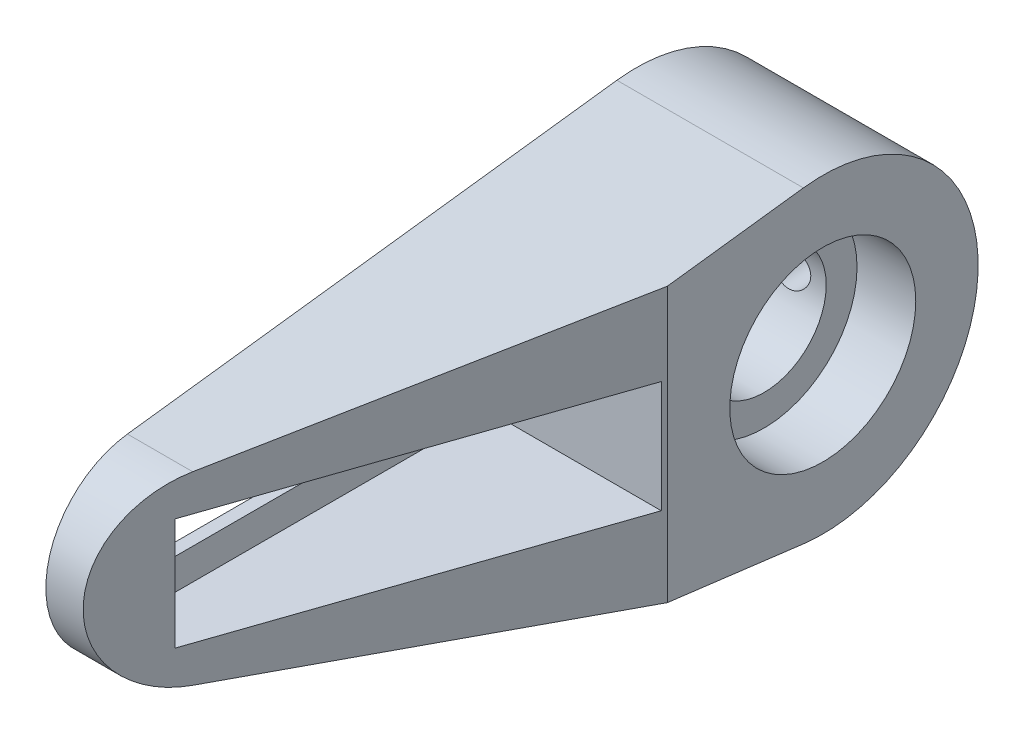
SolidWorks part; units mm, degrees
material "PLA"
ref_plane "Front Plane" through (0, 0, 0) normal (0, 0, 1) x (1, 0, 0)
ref_plane "Top Plane" through (0, 0, 0) normal (0, 1, 0) x (1, 0, 0)
ref_plane "Right Plane" through (0, 0, 0) normal (1, 0, 0) x (0, 0, -1)
sketch "Sketch1" plane through (0, 0, 0) normal (1, 0, 0) x (0, 0, -1)
  circle A0 centre (0, 0) radius 9.5
  circle A1 centre (0, 0) radius 15.875
  circle A2 centre (0, 0) radius 6.35
  dimension "D1" = 19
  dimension "D2" = 31.75
  dimension "D3" = 12.7
extrude "Boss-Extrude1" add sketch "Sketch1" along normal blind 6 contours A1 A0 region at (0, 0, 15.426)
extrude "Boss-Extrude2" add sketch "Sketch1<3>" against normal blind 13.05 contours A0 A2 | A1 A0 region at (0, 0, 9.2313) region at (0, 0, 15.426)
sketch "Sketch1<3>" plane through (0, 0, 0) normal (1, 0, 0) x (0, 0, -1) same geometry as "Sketch1"
sketch "Sketch2" plane through (-13.05, 0, 0) normal (-1, 0, 0) x (0, 0, 1)
  line L0 (0, 0) -> (11.1567, 0) construction
  circle A0 centre (0, 12.7) radius 1.95
  circle A1 centre (0, 0) radius 15.875
  circle A2 centre (0, 0) radius 15.875
  circle A3 centre (0, -12.7) radius 1.95
  dimension "D2" = 3.9
  dimension "D3" = 12.7
  dimension "D1" = 0
extrude "Cut-Extrude1" cut sketch "Sketch2" against normal blind 10.16 contours A0 | A3 region at (-13.05, 12.7, 0) region at (-13.05, -12.7, 0)
ref_plane "Plane1" through (0, 0, -15.875) normal (0, 0, 1) x (1, 0, 0)
sketch "Sketch3" plane through (0, 0, -15.875) normal (0, 0, 1) x (1, 0, 0)
  line L0 (-3.525, 0) -> (5.8573, 0) construction
  line L1 (-3.525, 0) -> (-3.525, 15.875) construction
  line L2 (6, 15.875) -> (-13.05, 15.875) construction
  circle A0 centre (-3.525, 0) radius 1.95
  dimension "D1" = 3.9
extrude "Cut-Extrude2" cut sketch "Sketch3" along normal up to surface (9.525 mm away) up to face at (-13.05, 0, -6.35)
sketch "Sketch4" plane through (6, 0, 0) normal (1, 0, 0) x (0, 0, -1)
  line L0 (-1.9844, 15.7505) -> (-51.9906, 9.4503)
  line L1 (0, 0) -> (-50.8, 0) construction
  line L2 (-1.9844, -15.7505) -> (-51.9906, -9.4503)
  circle A0 centre (0, 0) radius 15.875 construction
  circle A1 centre (-50.8, 0) radius 9.525
  circle M6 centre (0, 0) radius 15.875
  dimension "D1" = 50.8
  dimension "D2" = 19.05
extrude "Boss-Extrude3" add sketch "Sketch4" against normal up to surface (19.05 mm away) contours A1 | A1 L2 M6 | A1 L0 M6 region at (6, 0, 27.4958) region at (6, 0, 50.8) up to face at (-13.05, 0, -15.875)
sketch "Sketch5" plane through (0, 0, 0) normal (0, 1, 0) x (1, 0, 0)
  line L0 (-13.05, -51.9906) -> (-13.05, -60.325) construction
  line L1 (-13.05, -51.9906) -> (6, -51.9906) construction
  line L2 (6, -60.325) -> (6, -51.9906) construction
  line L3 (-13.05, -1.9844) -> (-13.05, -51.9906) construction
  line L4 (6, -51.9906) -> (6, -1.9844) construction
  line L5 (-13.05, 6.35) -> (-13.05, -6.35) construction
  line L6 (-13.05, 6.35) -> (-13.05, -6.35)
  line L7 (-13.05, 0) -> (8.4889, 0) construction
  line L8 (-13.05, -51.9906) -> (-13.05, -60.325)
  line L9 (-13.05, -51.9906) -> (6, -51.9906)
  line L10 (6, -60.325) -> (6, -51.9906)
  line L11 (-13.05, -1.9844) -> (-13.05, -51.9906)
  line L12 (6, -51.9906) -> (6, -1.9844)
  line L14 (-5.475, 15.875) -> (-13.05, 15.875) construction
  line L15 (-5.475, 15.875) -> (-13.05, 15.875)
  line L16 (-13.05, -15.875) -> (2.19, -60.325)
  line L17 (-5.475, -15.875) -> (-13.05, -15.875)
  line L18 (-13.05, -60.325) -> (6, -60.325) construction
  line L19 (2.19, -60.325) -> (6, -60.325)
  line L20 (-13.05, -51.9906) -> (-13.05, -15.875)
  line L21 (2.19, -60.325) -> (-13.05, -60.325)
  line L22 (-5.475, -15.875) -> (6, -15.875)
  line L23 (6, -15.875) -> (-9.24, -60.325)
  dimension "D1" = 3.81
  dimension "D2" = 3.81
extrude "Cut-Extrude3" cut sketch "Sketch5" against normal through all both and the other way through all contours L16 L23 L9 | L9 L23 L21 L16 | L16 L19 L10 L9 | L12 L23 L16 L9 region at (-3.525, 0, 49.2125) region at (-3.525, 0, 56.6208) region at (2.5159, 0, 38.8482) region at (3.3157, 0, 55.779)
sketch "Sketch7" plane through (6, 0, 0) normal (1, 0, 0) x (0, 0, -1)
  line L0 (-34.84, 5.715) -> (-34.84, -5.715) construction
  line L1 (-53.34, -5.715) -> (-16.34, -5.715)
  line L2 (-53.34, -5.715) -> (-53.34, 5.715)
  line L3 (-15.875, -14.0004) -> (-15.875, 14.0004)
  line L4 (-15.875, 14.0004) -> (-51.9906, 9.4503)
  line L5 (-51.9906, -9.4503) -> (-15.875, -14.0004)
  line L6 (-15.875, -14.0004) -> (-15.875, 14.0004)
  line L7 (-15.875, 14.0004) -> (-51.9906, 9.4503)
  line L8 (-51.9906, -9.4503) -> (-15.875, -14.0004)
  line L9 (-53.34, 5.715) -> (-16.34, 5.715)
  line L10 (-16.34, -5.715) -> (-16.34, 5.715)
  line L11 (-53.34, -5.715) -> (-16.34, 5.715) construction
  line L12 (-53.34, 5.715) -> (-16.34, -5.715) construction
  line L13 (-49.59, 0) -> (-20.09, 0) construction
  line L14 (-48.81, -2.54) -> (-20.87, -2.54)
  line L15 (-48.81, -2.54) -> (-48.81, 2.54)
  line L16 (-48.81, 2.54) -> (-20.87, 2.54)
  line L17 (-20.87, -2.54) -> (-20.87, 2.54)
  line L18 (-48.81, -2.54) -> (-20.87, 2.54) construction
  line L19 (-48.81, 2.54) -> (-20.87, -2.54) construction
  circle A0 centre (-50.34, 0) radius 0.75
  arc A1 (-51.9906, 9.4503) -> (-51.9906, -9.4503) centre (-50.8, 0) ccw
  arc A2 (-51.9906, 9.4503) -> (-51.9906, -9.4503) centre (-50.8, 0) ccw
  circle A3 centre (-19.34, 0) radius 0.75
  point P4 (-34.84, 0)
  point P16 (-34.84, 0)
  dimension "D5" = 1.5
  dimension "D2" = 11.43
  dimension "D3" = 37
  dimension "D4" = 2.54
  dimension "D6" = 31
  dimension "D7" = 5.08
  dimension "D8" = 27.94
  dimension "D1" = 0
extrude "Cut-Extrude4" cut sketch "Sketch7" against normal blind 17.78 contours L1 L10 L9 L2 L17 L14 L15 L16 A0 A3 | L14 L17 L16 L15 | A0 | A3 region at (6, 0, 52.9527) region at (6, 0, 34.84) region at (6, 0, 50.34) region at (6, 0, 19.34)
extrude "Cut-Extrude5" cut sketch "Sketch7<3>" against normal through all contours A0 | L14 L17 L16 L15 | A3 region at (6, 0, 34.84) region at (6, 0, 50.34) region at (6, 0, 19.34)
sketch "Sketch7<3>" plane through (6, 0, 0) normal (1, 0, 0) x (0, 0, -1) same geometry as "Sketch7"
